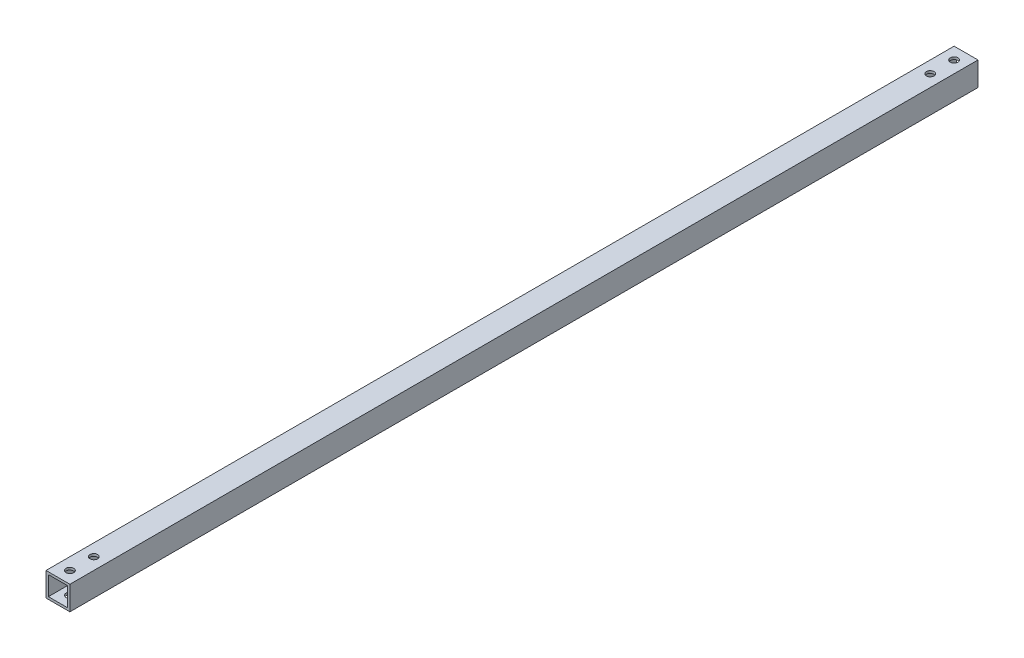
SolidWorks part; units mm, degrees
material "5052-H34"
ref_plane "正面" through (0, 0, 0) normal (0, 0, 1) x (1, 0, 0)
ref_plane "平面" through (0, 0, 0) normal (0, 1, 0) x (1, 0, 0)
ref_plane "右側面" through (0, 0, 0) normal (1, 0, 0) x (0, 0, -1)
sketch "ｽｹｯﾁ1" plane through (0, 0, 0) normal (0, 0, 1) x (1, 0, 0)
  line L1 (-5, 5) -> (5, 5)
  line L2 (-5, 5) -> (-5, -5)
  line L3 (-5, -5) -> (5, -5)
  line L4 (5, 5) -> (5, -5)
  line L5 (-5, 5) -> (5, -5) construction
  line L6 (-5, -5) -> (5, 5) construction
  point P0 (0, 0)
  dimension "D1" = 10
  dimension "D2" = 10
extrude "押し出し-薄板1" add sketch "ｽｹｯﾁ1" along normal blind 380 thin thin type one direction reverse wall 1
sketch "ｽｹｯﾁ2" plane through (0, 5, 0) normal (0, 1, 0) x (1, 0, 0)
  line L0 (-5, -190) -> (5, -190) construction
  line L1 (-5, -380) -> (-5, 0) construction
  line L2 (5, -380) -> (5, 0) construction
  line L3 (0, 0) -> (0, -5) construction
  line L4 (0, -5) -> (0, -15) construction
  circle A0 centre (0, -5) radius 1.6
  circle A1 centre (0, -375) radius 1.6
  circle A2 centre (0, -15) radius 1.6
  circle A3 centre (0, -365) radius 1.6
  dimension "D1" = 3.2
  dimension "D2" = 5
  dimension "D3" = 10
extrude "ｶｯﾄ - 押し出し1" cut sketch "ｽｹｯﾁ2" against normal through all
